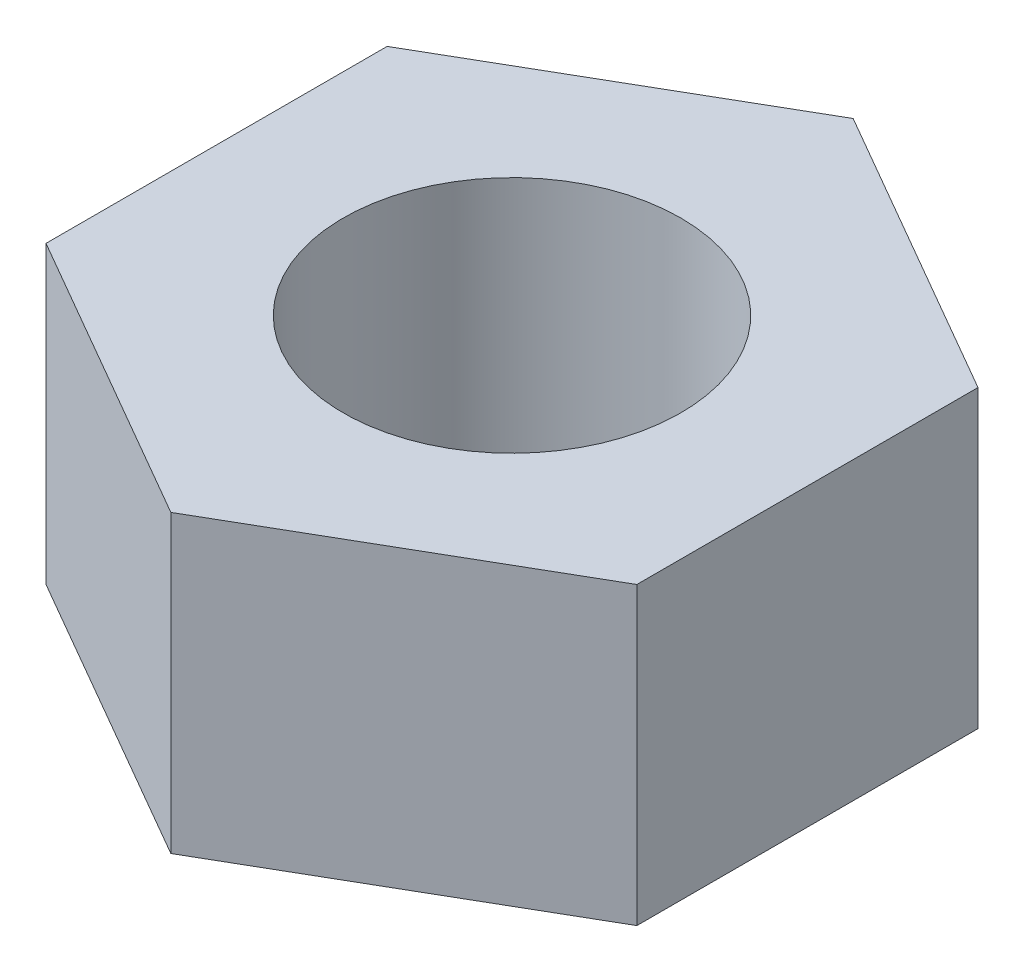
SolidWorks part; units mm, degrees
ref_plane "Front Plane" through (0, 0, 0) normal (0, 0, 1) x (1, 0, 0)
ref_plane "Top Plane" through (0, 0, 0) normal (0, 1, 0) x (1, 0, 0)
ref_plane "Right Plane" through (0, 0, 0) normal (1, 0, 0) x (0, 0, -1)
sketch "Sketch1" plane through (0, 0, 0) normal (0, 0, 1) x (1, 0, 0)
  line L0 (0, -2.7781) -> (0, 2.7781) construction
  line L1 (5.5562, 0) -> (-5.5562, 0) construction
  line L2 (3.175, -2.7781) -> (-3.175, -2.7781) construction
  line L3 (3.175, -2.7781) -> (3.175, -1.5081) construction
  point P4 (0, 0)
  point P8 (0, 0)
  point P11 (0, -2.7781)
  dimension "Height" = 5.5562
  dimension "Width" = 11.1125
  dimension "Thread Size" = 6.35
  dimension "Thread Pitch" = 1.27
sketch "Sketch2" plane through (0, 0, 0) normal (1, 0, 0) x (0, 0, -1)
  line L0 (0, -2.7781) -> (0, 2.7781) construction
  line L1 (3.048, -3.3433) -> (-3.048, -3.3433)
  line L2 (3.048, -3.3433) -> (3.048, 2.7781)
  line L3 (3.048, 2.7781) -> (-3.048, 2.7781)
  line L4 (-3.048, -3.3433) -> (-3.048, 2.7781)
  line L5 (3.048, -3.3433) -> (-3.048, 2.7781) construction
  line L6 (3.048, 2.7781) -> (-3.048, -3.3433) construction
  point P0 (0, -0.2826)
  point P7 (0, 2.7781)
  dimension "Minimum Slot Width" = 6.096
  dimension "Minimum Slot Depth" = 6.1214
sketch "Sketch11" plane through (0, 0, 0) normal (0, 1, 0) x (1, 0, 0)
  line L1 (0, 6.4158) -> (-5.5562, 3.2079)
  line L2 (-5.5562, 3.2079) -> (-5.5562, -3.2079)
  line L3 (-5.5562, -3.2079) -> (0, -6.4158)
  line L4 (0, -6.4158) -> (5.5562, -3.2079)
  line L5 (5.5562, -3.2079) -> (5.5562, 3.2079)
  line L6 (5.5562, 3.2079) -> (0, 6.4158)
  circle A0 centre (0, 0) radius 5.5563 construction
  circle A1 centre (0, 0) radius 3.175
  point P19 (0, -3.175)
extrude "Boss-Extrude1" add sketch "Sketch11" along normal up to vertex (2.7781 mm away) and the other way up to vertex (2.7781 mm away) up to point (0, 2.7781, 0) other way up to point (0, -2.7781, 0)
fillet "Fillet1" [suppressed] radius 0.3334
sketch "Sketch3" plane through (0, 0, 0) normal (1, 0, 0) x (0, 0, -1)
  line L1 (3.2079, 2.7781) -> (6.4158, 2.7781) construction
  line L2 (5.0006, -2.7781) -> (6.4158, -1.9611)
  line L3 (3.2079, -2.7781) -> (6.4158, -2.7781) construction
  line L4 (6.4158, 2.7781) -> (6.4158, -2.7781) construction
  line L5 (6.4158, -1.9611) -> (6.4158, -2.7781)
  line L7 (5.1118, 2.7781) -> (6.4158, 2.0252)
  line L8 (6.4158, 2.0252) -> (6.4158, 2.7781)
  line L10 (5.0006, -2.7781) -> (6.4158, -2.7781)
  line L12 (5.1118, 0) -> (5.5563, 0) construction
  line L16 (5.1118, 2.7781) -> (6.4158, 2.7781)
  line L21 (3.175, -2.7781) -> (3.175, -2.6194)
  line L22 (-3.2079, -2.7781) -> (3.2079, -2.7781) construction
  line L24 (3.3338, -2.7781) -> (3.175, -2.7781)
  line L25 (3.175, -2.6194) -> (3.3338, -2.7781)
  line L26 (3.175, 2.7781) -> (3.175, 2.6194)
  line L27 (3.175, 2.7781) -> (3.3338, 2.7781)
  line L28 (3.3338, 2.7781) -> (3.175, 2.6194)
  line L29 (3.048, 2.7781) -> (-3.048, 2.7781) construction
  line L30 (3.3338, 0) -> (3.7783, 0) construction
  line L31 (4.6673, 0) -> (5.1118, 0) construction
  line L32 (3.7783, 0) -> (4.2228, 0) construction
  line L33 (4.2228, 0) -> (4.6673, 0) construction
  point P0 (5.1118, 2.7781)
  point P1 (5.5563, 0)
  point P14 (3.175, 0)
  point P36 (5.5563, -2.7781)
  point P44 (5.334, 0)
  dimension "D2" = 30
  dimension "D5" = 0.1588
  dimension "D7" = 0.5556
  dimension "D1" = 30
revolve "Cut-Revolve2" [suppressed] cut sketch "Sketch3" angle 360 about L0
sketch "Sketch15" [suppressed] plane through (16.2719, 0, 15.8104) normal (0.5, 0, -0.866) x (-0.866, 0, -0.5)
  line L0 (21.997, 2.5215) -> (21.997, 1.2768) construction
  line L1 (21.997, -1.2126) -> (21.997, 0.0321) construction
  line L2 (21.997, 0.0321) -> (21.997, 1.2768) construction
  line L3 (21.997, -1.2126) -> (21.997, -2.4573) construction
  line L6 (21.2784, 0.0321) -> (21.6377, -0.5903)
  line L7 (21.6377, -0.5903) -> (22.3564, -0.5903)
  line L8 (22.3564, -0.5903) -> (22.7157, 0.0321)
  line L9 (22.7157, 0.0321) -> (22.3564, 0.6544)
  line L10 (22.3564, 0.6544) -> (21.6377, 0.6544)
  line L11 (21.6377, 0.6544) -> (21.2784, 0.0321)
  circle A0 centre (21.997, 0.0321) radius 0.6224 construction
  spline S4 degree 3 poles (18.7891, 2.0252) (19.8367, 2.3276) (20.9, 2.5208) (22.2636, 2.5217) (22.5377, 2.5101) (23.0797, 2.4648) (23.3489, 2.4312) (24.1517, 2.3016) (24.6805, 2.1766) (25.2049, 2.0252) knots 0 0 0 0 0.5 0.5 0.625 0.625 0.75 0.75 1 1 1 1 construction
  spline S5 degree 3 poles (25.2049, -1.9611) (24.1574, -2.2635) (23.0941, -2.4566) (21.7304, -2.4575) (21.4564, -2.4459) (20.9144, -2.4007) (20.6452, -2.3671) (19.8424, -2.2374) (19.3136, -2.1125) (18.7891, -1.9611) knots 0 0 0 0 0.5 0.5 0.625 0.625 0.75 0.75 1 1 1 1 construction
  point P1 (21.997, 0.6544)
  point P6 (21.997, 0)
extrude "Cut-Extrude2" [suppressed] cut sketch "Sketch15" along normal blind 0.1588
sketch "Sketch18" [suppressed] plane through (0, 2.7781, 0) normal (0, 1, 0) x (1, 0, 0)
  line L0 (0, 0) -> (0, -5.1118) construction
  line L1 (0, 0) -> (-2.9859, -2.9859) construction
  line L2 (0, 0) -> (-1.0929, -4.0789) construction
  line L3 (-5.1118, 0) -> (-4.7562, 0) construction
  line L4 (-4.7562, 0) -> (-4.4006, 0) construction
  line L5 (-4.4006, 0) -> (-4.045, 0) construction
  line L6 (-4.045, 0) -> (-3.6894, 0) construction
  line L7 (-3.6894, 0) -> (-3.3338, 0) construction
  line L8 (0, 0) -> (-2.7781, -4.8119) construction
  line L9 (-5.5562, -3.2079) -> (0, -6.4158) construction
  circle A0 centre (0, 0) radius 5.1118 construction
  circle A1 centre (0, 0) radius 3.3338 construction
  arc A2 (-2.9859, -2.9859) -> (-1.0929, -4.0789) centre (0, 0) ccw construction
  arc A3 (-3.1117, -3.1117) -> (-1.1389, -4.2506) centre (0, 0) ccw
  arc A4 (-2.8602, -2.8602) -> (-1.0469, -3.9071) centre (0, 0) ccw
  arc A5 (-2.8602, -2.8602) -> (-3.1117, -3.1117) centre (-2.9859, -2.9859) ccw
  arc A6 (-1.1389, -4.2506) -> (-1.0469, -3.9071) centre (-1.0929, -4.0789) ccw
  arc A7 (2.9859, -2.9859) -> (1.0929, -4.0789) centre (0, 0) cw construction
  arc A8 (3.1117, -3.1117) -> (1.1389, -4.2506) centre (0, 0) cw
  arc A9 (2.8602, -2.8602) -> (1.0469, -3.9071) centre (0, 0) cw
  arc A10 (2.8602, -2.8602) -> (3.1117, -3.1117) centre (2.9859, -2.9859) cw
  arc A11 (1.1389, -4.2506) -> (1.0469, -3.9071) centre (1.0929, -4.0789) cw
  point P18 (-2.1114, -3.657)
  point P30 (2.1114, -3.657)
  dimension "D1" = 30
extrude "Cut-Extrude3" [suppressed] cut sketch "Sketch18" against normal blind 0.1984
sketch "Sketch5" [suppressed] plane through (0, 0, 0) normal (0, 1, 0) x (1, 0, 0)
  circle A1 centre (0, 0) radius 3.175 construction
  point P0 (0, -3.175)
sketch "Sketch6" [suppressed] plane through (0, 0, 0) normal (0, 0, 1) x (1, 0, 0)
  line L0 (3.175, 2.7781) -> (3.175, -2.7781)
  line L2 (0, -2.7781) -> (5.5562, -2.7781) construction
  line L3 (3.175, -2.7781) -> (0, -2.7781)
  line L4 (0, -2.7781) -> (0, 2.7781)
  line L5 (0, -2.7781) -> (0, 2.7781) construction
  line L6 (0, 2.7781) -> (3.175, 2.7781)
revolve "Revolve2" [suppressed] add sketch "Sketch6" angle 360 about L4
sketch "Sketch7" [suppressed] plane through (0, -2.7781, 0) normal (0, -1, 0) x (1, 0, 0)
  circle A2 centre (0, 0) radius 3.175
  circle A3 centre (0, 0) radius 3.175
  dimension "D1" = 0
curve "Helix/Spiral1" [suppressed] pitch 1.27 height 5.5562 turns 4.375
sketch "Sketch8" [suppressed] plane through (0, 0, 0) normal (0, 0, 1) x (1, 0, 0)
  line L0 (3.3125, -2.6987) -> (2.2126, -3.3337) construction
  line L1 (2.2126, -3.3337) -> (3.3125, -3.9687) construction
  line L2 (3.3125, -3.9687) -> (3.3125, -2.6987) construction
  line L3 (2.3501, -3.2544) -> (2.3501, -3.4131)
  line L4 (3.175, -2.7781) -> (3.175, -3.8894) construction
  line L5 (3.175, -3.3337) -> (3.3125, -3.3337) construction
  line L6 (2.2126, -3.3337) -> (2.3501, -3.3337) construction
  line L7 (3.2437, -3.3337) -> (3.2437, -3.9291) construction
  line L8 (2.3501, -3.2544) -> (3.3125, -2.6987)
  line L9 (3.3125, -2.6987) -> (3.2437, -3.9291)
  line L10 (2.3501, -3.4131) -> (3.2437, -3.9291)
  dimension "D1" = 1.27
  dimension "D2" = 0.1588
sweep "Cut-Sweep1" [suppressed] cut profiles "Sketch8" path "Helix/Spiral1"
sketch "Sketch9" [suppressed] plane through (0, 0, 0) normal (0, 0, 1) x (1, 0, 0)
  line L0 (0, 0.3969) -> (0, -2.7781)
  line L1 (0, 0.3969) -> (0, 0.5556)
  line L2 (0, -2.7781) -> (3.175, -2.7781)
  line L3 (3.175, -2.7781) -> (3.3337, -2.7781)
  line L4 (3.3337, -2.7781) -> (0, 0.5556)
  dimension "D1" = 0.1588
revolve "Revolve3" [suppressed] add sketch "Sketch9" angle 360 about L0
sketch "Sketch14" [suppressed] plane through (0, 0, 0) normal (0, 0, 1) x (1, 0, 0)
  line L0 (3.3337, 2.7781) -> (0, 2.7781)
  line L1 (0, 2.7781) -> (0, -0.5556)
  line L2 (0, -0.5556) -> (3.3337, 2.7781)
revolve "Revolve4" [suppressed] add sketch "Sketch14" angle 360 about L1
sketch "Sketch10" [suppressed] plane through (0, -2.7781, 0) normal (0, -1, 0) x (1, 0, 0)
  circle A0 centre (0, 0) radius 3.3338 construction
  circle A1 centre (0, 0) radius 3.3338
extrude "Boss-Extrude2" [suppressed] add sketch "Sketch10" against normal up to surface (5.5563 mm away) up to face at (0, 2.7781, 0)
combine bodies "Combine1" [suppressed] operation type subtract main body 110 bodies to subtract 120
equation "\"D5@Sketch3\"=\"Thread Size@Sketch1\"*.025"
equation "\"D4@Helix/Spiral1\" = \"Thread Pitch@Sketch1\""
equation "\"D3@Helix/Spiral1\" = \"Height@Sketch1\""
equation "\"D1@Sketch8\" = \"Thread Pitch@Sketch1\""
equation "\"D2@Sketch8\" = \"Thread Pitch@Sketch1\" / 8"
equation "\"D1@Sketch9\"=\"Thread Size@Sketch1\" * .025"
equation "\"D1@Fillet1\"=\"Width@Sketch1\" * .03"
equation "\"D7@Sketch3\"=\"Width@Sketch1\"*.05"
equation "\"D1@Cut-Extrude2\" =  (  ( \"Width@Sketch1\" - \"Thread Size@Sketch1\" / 2 )  * .02 ) "
equation "\"D1@Cut-Extrude3\"=((\"width@sketch1\"-\"Thread Size@sketch1\"/2)*.025)"
